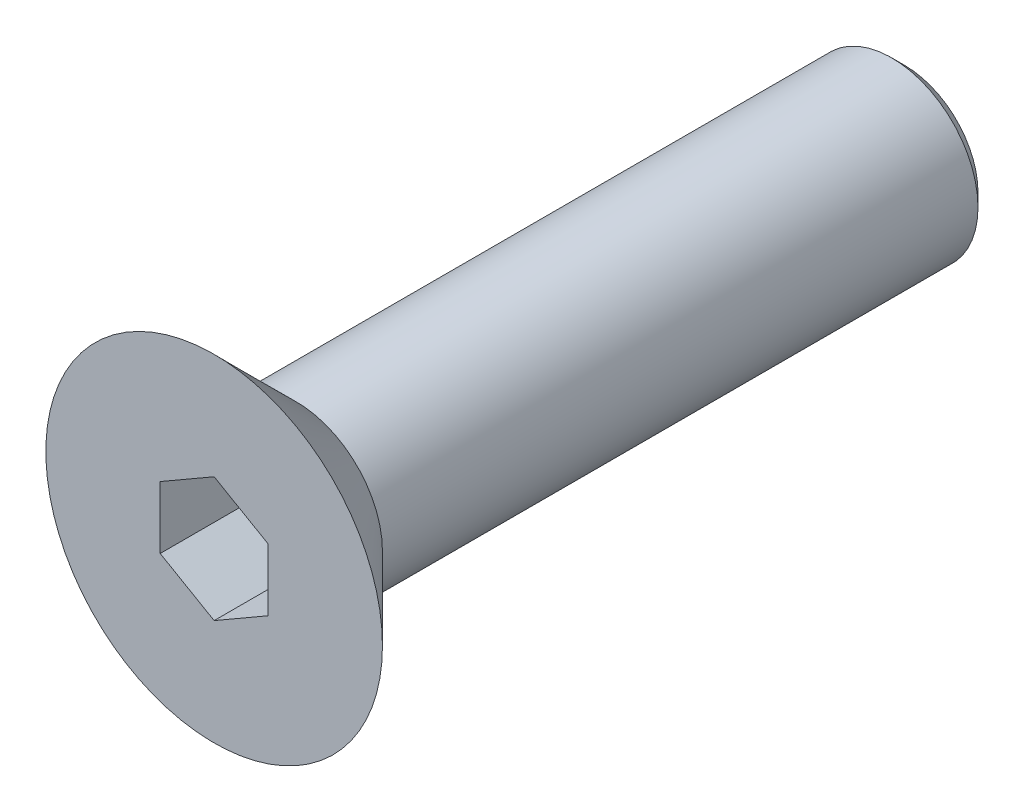
SolidWorks part; units mm, degrees
ref_plane "Front Plane" through (0, 0, 0) normal (0, 0, 1) x (1, 0, 0)
ref_plane "Top Plane" through (0, 0, 0) normal (0, 1, 0) x (1, 0, 0)
ref_plane "Right Plane" through (0, 0, 0) normal (1, 0, 0) x (0, 0, -1)
sketch "Sketch1" plane through (0, 0, 0) normal (0, 0, 1) x (1, 0, 0)
  circle A0 centre (0, 0) radius 4
  dimension "D1" = 8
extrude "Boss-Extrude1" add sketch "Sketch1" along normal blind 2.3
sketch "Sketch2" plane through (0, 0, 0) normal (0, 0, -1) x (-1, 0, 0)
  circle A0 centre (0, 0) radius 2
  dimension "D1" = 4
extrude "Boss-Extrude2" add sketch "Sketch2" along normal blind 13.7
chamfer "Chamfer1" distance 0.3 angle 45 1 edges at (-2, 0, -13.7)
sketch "Sketch3" plane through (0, 0, 2.3) normal (0, 0, 1) x (1, 0, 0)
  line L1 (0, 1.4434) -> (-1.25, 0.7217)
  line L2 (-1.25, 0.7217) -> (-1.25, -0.7217)
  line L3 (-1.25, -0.7217) -> (0, -1.4434)
  line L4 (0, -1.4434) -> (1.25, -0.7217)
  line L5 (1.25, -0.7217) -> (1.25, 0.7217)
  line L6 (1.25, 0.7217) -> (0, 1.4434)
  circle A0 centre (0, 0) radius 1.25 construction
  dimension "D1" = 2.5
extrude "Cut-Extrude1" cut sketch "Sketch3" against normal blind 2
chamfer "Chamfer2" distance 2.4 angle 45 1 edges at (4, 0, 0)
